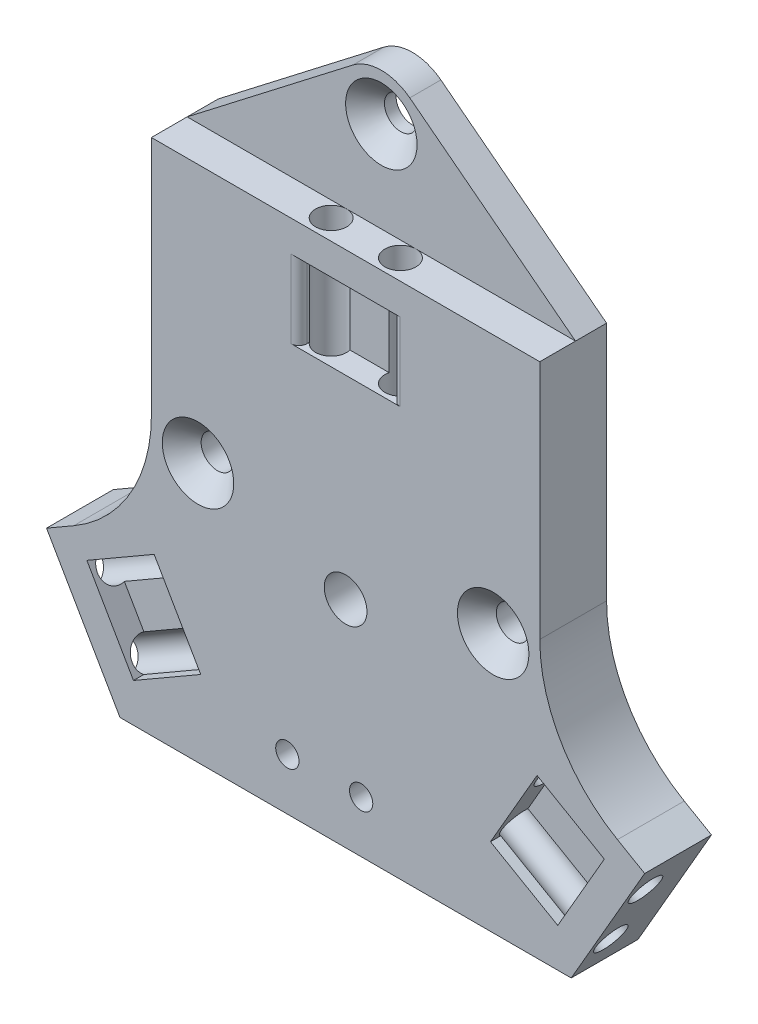
SolidWorks part; units mm, degrees
other "carriage coupler plate"
material "PET"
ref_plane "Front" through (0, 0, 0) normal (0, 0, 1) x (1, 0, 0)
ref_plane "Top" through (0, 0, 0) normal (0, 1, 0) x (1, 0, 0)
ref_plane "Right" through (0, 0, 0) normal (1, 0, 0) x (0, 0, -1)
sketch "Sketch1" plane through (0, 0, 0) normal (0, 0, 1) x (1, 0, 0)
  line L0 (0, 0) -> (0, 30) construction
  line L1 (0, 0) -> (25.9808, -15) construction
  line L2 (0, 0) -> (-25.9808, -15) construction
  dimension "D1" = 120
  dimension "D2" = 120
  dimension "D3" = 30
ref_plane "Plane1" through (0, 30, 0) normal (0, 1, 0) x (1, 0, 0)
sketch "Sketch2" plane through (0, 30, 0) normal (0, 1, 0) x (1, 0, 0)
  line L0 (-4.4589, 0) -> (0, -4.0148) construction
  line L1 (0, 0) -> (-25.9808, 0) construction
  line L2 (0, 0) -> (0, -4.0148) construction
  line L3 (-4.4589, 0) -> (0, 0) construction
  line L4 (0, -5.3962) -> (0, -4.0148) construction
  line L5 (0, -5.3962) -> (-4.4589, 0) construction
  line L7 (-4, -4.0148) -> (4, -4.0148) construction
  line L8 (3.9519, -3.3962) -> (-3.9519, -3.3962) construction
  line L9 (0, -0.3962) -> (0, -3.3962) construction
  line L10 (0, -4.0148) -> (0, -7.3926) construction
  circle A0 centre (-4.4589, 0) radius 2
  circle A1 centre (4.4589, 0) radius 2
  circle A2 centre (0, -4.0148) radius 4
  circle A3 centre (0, -5.3962) radius 5 construction
  circle A4 centre (0, -7.3926) radius 1.5
  dimension "D1" = 4
  dimension "D2" = 8
  dimension "D4" = 10
  dimension "D9" = 3
  dimension "D6" = 7.3926
  dimension "D8" = 8.9177
  dimension "D3" = 42
  dimension "D5" = 50.433
  dimension "D7" = 3.3962
  dimension "D10" = 0.6186
sketch "Sketch3" plane through (0, 0, 0) normal (0, 0, 1) x (1, 0, 0)
  line L0 (0, 30) -> (0, 35) construction
  line L2 (0, 35) -> (0, 39) construction
  line L3 (-25, 39) -> (25, 39)
  line L4 (25, 39) -> (25, -3.5116)
  line L5 (25, -3.5116) -> (38.5044, -11.3084)
  line L6 (0, 0) -> (0, 30) construction
  line L7 (-25, -3.5116) -> (-38.5044, -11.3084)
  line L8 (-25, 39) -> (-25, -3.5116)
  line L9 (4.4589, 30) -> (4.4589, 39) construction
  line L10 (25.9808, -15) -> (33.775, -19.5) construction
  line L11 (29.0456, -27.6916) -> (-29.0456, -27.6916)
  line L13 (0, 0) -> (25.9808, -15) construction
  line L14 (33.775, -19.5) -> (38.5044, -11.3084)
  line L15 (4.4589, 30) -> (0, 30) construction
  line L16 (4.4589, 30) -> (9.4589, 30) construction
  line L17 (-33.775, -19.5) -> (-38.5044, -11.3084)
  line L18 (33.775, -19.5) -> (29.0456, -27.6916)
  line L19 (-33.775, -19.5) -> (-29.0456, -27.6916)
  dimension "D1" = 5
  dimension "D2" = 4
  dimension "D3" = 25
  dimension "D4" = 120
  dimension "D5" = 5
  dimension "D6" = 9.4589
  dimension "D7" = 9.4589
  dimension "D8" = 9
  dimension "D9" = 9
extrude "Boss-Extrude1" add sketch "Sketch3" along normal blind 2.6 and the other way blind 6
fillet "Fillet1" radius 20 2 edges at (-25, -3.5116, -1.7) (25, -3.5116, -1.7)
sketch "Sketch4" plane through (0, 30, 0) normal (0, 1, 0) x (1, 0, 0)
  line L0 (0, -0.0148) -> (0, 0.4852) construction
  line L1 (5.1148, 0.4852) -> (-5.1148, 0.4852)
  line L2 (-5.1148, 0.4852) -> (-6, -0.4)
  line L3 (-6, -0.4) -> (-6, -2.6)
  line L4 (25, -2.6) -> (-25, -2.6) construction
  line L5 (-6, -2.6) -> (6, -2.6)
  line L7 (0, -5.3962) -> (-4.4589, 0) construction
  line L8 (-0.7342, -4.5076) -> (-0.5833, -4.3426)
  line L9 (6, -0.4) -> (6, -2.6)
  line L10 (5.1148, 0.4852) -> (6, -0.4)
  circle A7 centre (0, -4.0148) radius 4 construction
  dimension "D1" = 0.5
  dimension "D2" = 135
  dimension "D3" = 12
  dimension "D4" = 2.2
extrude "Cut-Extrude1" cut sketch "Sketch4" against normal blind 5 and the other way blind 5 contours L5 L9 L10 L1 L2 L3
sketch "Sketch5" plane through (0, 39, 0) normal (0, 1, 0) x (1, 0, 0)
  circle A0 centre (-4.4589, 0) radius 2 construction
  circle A1 centre (4.4589, 0) radius 2 construction
  circle A2 centre (-4.4589, 0) radius 2
  circle A3 centre (4.4589, 0) radius 2
extrude "Cut-Extrude2" cut sketch "Sketch5" against normal blind 20
fillet "Fillet3" radius 1 2 edges at (-6, 30, 2.6) (6, 30, 2.6)
ref_axis "Axis1" through (0, 0, -80.9) along (0, 0, 1)
pattern_circular "CirPattern1" count 3 over 360 about axis through (0, 0, -80.9) along (0, 0, 1) of "Cut-Extrude2", "Cut-Extrude1"
sketch "Sketch6" plane through (0, 0, 2.6) normal (0, 0, 1) x (1, 0, 0)
  circle A0 centre (0, 0) radius 2.75
  dimension "D1" = 5.5
extrude "Cut-Extrude3" cut sketch "Sketch6" against normal through all
sketch "Sketch7" plane through (0, 0, -6) normal (0, 0, -1) x (-1, 0, 0)
  line L0 (-25, 39) -> (-3.6637, 55.4515)
  line L1 (25, 39) -> (3.6637, 55.4515)
  line L2 (0, 0) -> (0, 50.7) construction
  line L3 (-25, 39) -> (25, 39) construction
  line L4 (-25, 39) -> (25, 39)
  arc A0 (3.6637, 55.4515) -> (-3.6637, 55.4515) centre (0, 50.7) ccw
  dimension "D1" = 12
  dimension "D2" = 11.7
extrude "Boss-Extrude2" add sketch "Sketch7" against normal blind 4
sketch "Sketch8" plane through (0, 0, 2.6) normal (0, 0, 1) x (1, 0, 0)
  line L0 (0, 0) -> (0, 50.7) construction
  line L1 (-19, 5.7) -> (19, 5.7) construction
  circle A0 centre (-19, 5.7) radius 2.1
  circle A1 centre (19, 5.7) radius 2.1
  circle A2 centre (0, 50.7) radius 2.1
  arc A3 (3.6637, 55.4515) -> (-3.6637, 55.4515) centre (0, 50.7) ccw construction
  point P10 (0, 5.7)
  dimension "D1" = 4.2
  dimension "D2" = 4.2
  dimension "D3" = 4.2
  dimension "D4" = 45
  dimension "D5" = 38
extrude "Cut-Extrude4" cut sketch "Sketch8" against normal through all
chamfer "Chamfer1" distance 2.5 angle 45 3 edges at (-16.9, 5.7, 2.6) (21.1, 5.7, 2.6) (-2.1, 50.7, -2)
sketch "Sketch9" plane through (0, 0, -6) normal (0, 0, -1) x (-1, 0, 0)
  line L0 (0, -27.6916) -> (0, -6.1064) construction
  line L1 (29.0456, -27.6916) -> (-29.0456, -27.6916) construction
  line L2 (-2, -21.0416) -> (7.5, -21.0416) construction
  circle A0 centre (7.5, -21.0416) radius 1.5
  circle A1 centre (-2, -21.0416) radius 1.5
  dimension "D4" = 3
  dimension "D5" = 3
  dimension "D1" = 6.65
  dimension "D2" = 7.5
  dimension "D3" = 9.5
extrude "Cut-Extrude5" cut sketch "Sketch9" against normal through all
